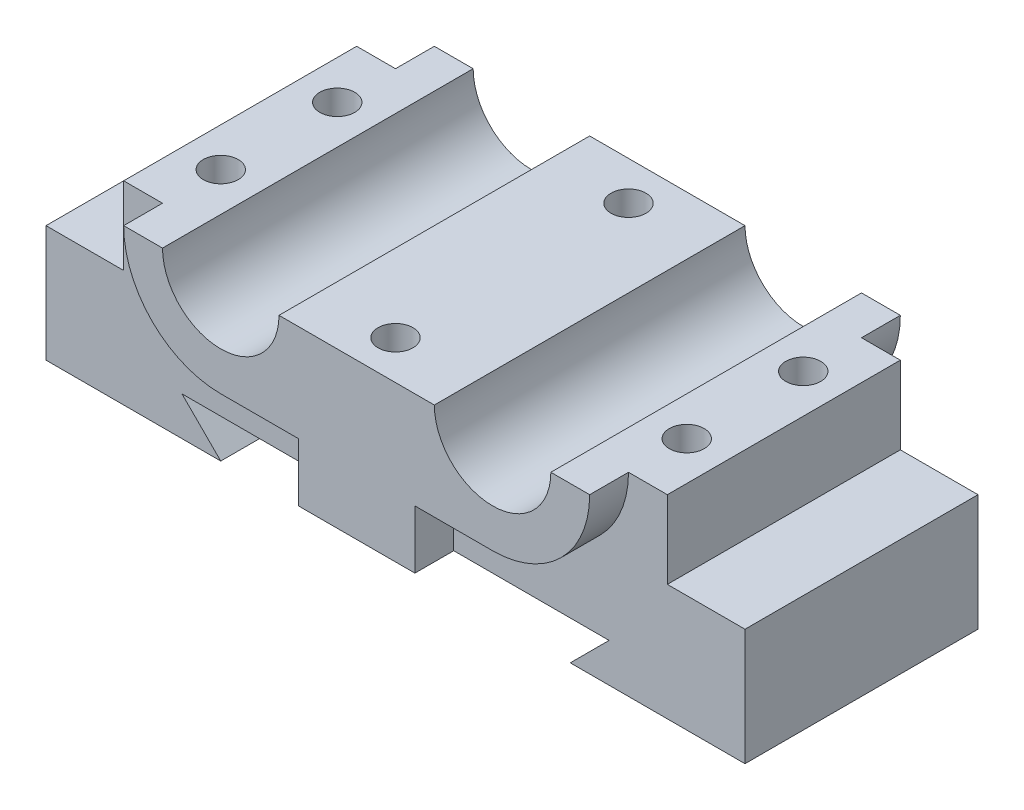
SolidWorks part; units mm, degrees
note: The reader was unsure of these and kept them because the rebuilt part matched: shared geometry of "Sketch1<3>".
ref_plane "Front Plane" through (0, 0, 0) normal (0, 0, 1) x (1, 0, 0)
ref_plane "Top Plane" through (0, 0, 0) normal (0, 1, 0) x (1, 0, 0)
ref_plane "Right Plane" through (0, 0, 0) normal (1, 0, 0) x (0, 0, -1)
sketch "Sketch1" plane through (0, 0, 0) normal (0, 0, 1) x (1, 0, 0)
  line L0 (0, 0) -> (-22.5, 0)
  line L1 (-22.5, 0) -> (-22.5, 15)
  line L2 (-22.5, 15) -> (-12.5, 15)
  line L3 (-12.5, 15) -> (-12.5, 25)
  line L4 (-12.5, 25) -> (-2.5, 25)
  line L5 (0, 0) -> (-5, 5)
  line L6 (-5, 5) -> (50, 5)
  line L7 (22.5, 31.2998) -> (22.5, -2.8829) construction
  line L8 (45, 0) -> (50, 5)
  line L9 (45, 0) -> (67.5, 0)
  line L10 (67.5, 0) -> (67.5, 15)
  line L11 (67.5, 15) -> (57.5, 15)
  line L12 (57.5, 15) -> (57.5, 25)
  line L13 (30, 5) -> (30, 12.5)
  line L14 (30, 12.5) -> (40, 12.5)
  line L15 (47.5, 25) -> (57.5, 25)
  line L16 (15, 5) -> (15, 12.5)
  line L17 (15, 12.5) -> (5, 12.5)
  line L18 (12.5, 25) -> (32.5, 25)
  arc A0 (32.5, 25) -> (47.5, 25) centre (40, 25) ccw
  arc A1 (40, 12.5) -> (52.5, 25) centre (40, 25) ccw
  arc A2 (5, 12.5) -> (-7.5, 25) centre (5, 25) cw
  arc A3 (12.5, 25) -> (-2.5, 25) centre (5, 25) cw
  point P12 (22.5, 5)
  point P17 (22.5, 25)
  point P25 (0, 0)
  point P26 (0, 0)
  dimension "D6" = 7.5
  dimension "D7" = 12.5
  dimension "D1" = 45
  dimension "D2" = 22.5
  dimension "D3" = 15
  dimension "D4" = 5
  dimension "D5" = 10
  dimension "D8" = 35
  dimension "D9" = 17.5
  dimension "D10" = 15
  dimension "D11" = 45
extrude "Boss-Extrude1" add sketch "Sketch1" along normal blind 5 contours L18 L7 L6 L13 L14 A1 L15 A0 | L7 L18 A3 L4 A2 L17 L16 L6
extrude "Boss-Extrude2" add sketch "Sketch1<3>" against normal blind 15 contours A1 L14 L13 L6 L8 L9 L10 L11 L12 L15 | L17 A2 L4 L3 L2 L1 L0 L5 L6 L16 | L7 L18 A3 L4 A2 L17 L16 L6 | L18 L7 L6 L13 L14 A1 L15 A0
sketch "Sketch1<3>" plane through (0, 0, 0) normal (0, 0, 1) x (1, 0, 0) same geometry as "Sketch1"
ref_plane "Plane1" through (0, 0, -15) normal (0, 0, -1) x (-1, 0, 0)
mirror "Mirror1" about plane through (0, 0, -15) normal (0, 0, -1) of bodies 102
sketch "Sketch2" plane through (0, 25, 0) normal (0, 1, 0) x (1, 0, 0)
  line L0 (22.5, 35) -> (22.5, -5) construction
  line L1 (12.5, 35) -> (32.5, 35) construction
  line L2 (12.5, -5) -> (32.5, -5) construction
  line L3 (52.5, 30) -> (52.5, 0) construction
  line L4 (-7.5, 30) -> (-7.5, 0) construction
  line L5 (-12.5, 7.5) -> (52.5, 7.5) construction
  line L6 (-12.5, 30) -> (-12.5, 0) construction
  line L7 (-12.5, 0) -> (-7.5, 0) construction
  line L8 (-7.5, 15) -> (52.5, 15) construction
  line L9 (-12.5, 22.5) -> (52.5, 22.5) construction
  line L10 (-7.5, 30) -> (52.5, 30)
  line L11 (-7.5, 0) -> (52.5, 0)
  dimension "D1" = 7.5
hole_wizard "Ø1.0mm Dowel Hole1" positions "3DSketch1" profile "Sketch3" hole size "Ø1.0" standard "ANSI Metric"
sketch3d "3DSketch1"
  line L0 (-7.5, 25, -30) -> (52.5, 25, -30) construction
  line L1 (-7.5, 25, 0) -> (52.5, 25, 0) construction
  line L2 (-7.5, 25, -30) -> (-7.5, 25, 0) construction
  line L3 (-12.5, 25, -22.5) -> (52.5, 25, -22.5) construction
  line L4 (-12.5, 25, -7.5) -> (52.5, 25, -7.5) construction
  point P0 (22.5, 25, -30)
  point P4 (22.5, 25, 0)
  point P8 (22.5, 25, -30)
  point P10 (52.5, 25, -22.5)
  point P13 (52.5, 25, -7.5)
  point P16 (-7.5, 25, -22.5)
  point P22 (-7.5, 25, -7.5)
  point P26 (22.5, 25, -30)
  point P28 (22.5, 25, 0)
  point P30 (22.5, 25, 0)
  point P32 (22.5, 25, 0)
  point P34 (22.5, 25, 0)
sketch "Sketch3" plane through (-7.5, 25, -7.5) normal (1, 0, 0) x (0, 0, 1)
  line L0 (0, 0) -> (0, 25)
  line L1 (0, 25) -> (2.25, 25)
  line L2 (2.25, 25) -> (2.25, 0)
  line L5 (2.25, 0) -> (0, 0)
  line L11 (0, -6.35) -> (0, 107.95) construction
  dimension "Thru Hole Dia." = 4.5
  dimension "Thru Hole Depth" = 25
sketch "Sketch5" plane through (0, 25, 0) normal (0, 1, 0) x (1, 0, 0)
  line L0 (-7.5, 30) -> (52.5, 30) construction
  line L1 (-7.5, 0) -> (52.5, 0) construction
  circle A0 centre (22.5, 30) radius 2.25
  circle A1 centre (22.5, 0) radius 2.25
  dimension "D1" = 4.5
extrude "Cut-Extrude1" cut sketch "Sketch5" against normal through all
